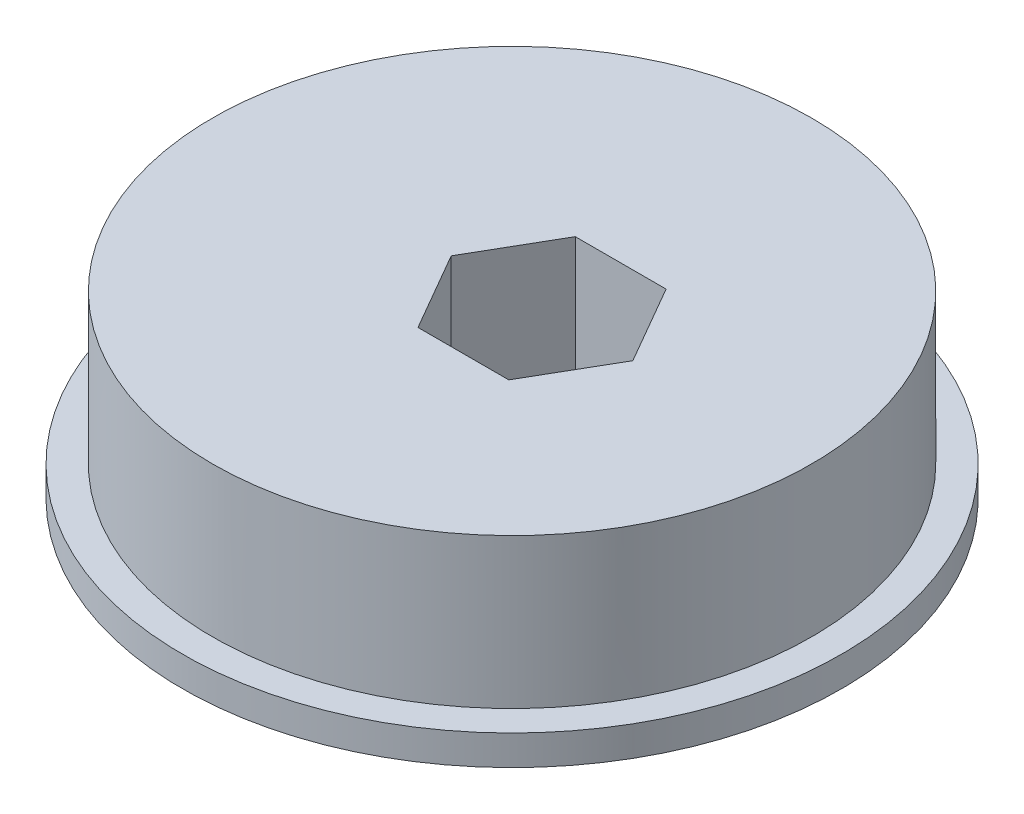
SolidWorks part; units mm, degrees
ref_plane "Front Plane" through (0, 0, 0) normal (0, 0, 1) x (1, 0, 0)
ref_plane "Top Plane" through (0, 0, 0) normal (0, 1, 0) x (1, 0, 0)
ref_plane "Right Plane" through (0, 0, 0) normal (1, 0, 0) x (0, 0, -1)
sketch "Sketch1" plane through (0, 0, 0) normal (0, 1, 0) x (1, 0, 0)
  line L0 (0, 0) -> (-1, 0) construction
  circle A1 centre (-1, 0) radius 10
  point P12 (0, 0)
  dimension "D3" = 20
  dimension "D2" = 1
extrude "Boss-Extrude1" add sketch "Sketch1" along normal blind 6
sketch "Sketch2" plane through (0, 0, 0) normal (0, -1, 0) x (1, 0, 0)
  line L0 (-12.8187, 0) -> (7.6603, 0) construction
  circle A0 centre (-1, 0) radius 11
  dimension "D2" = 22
  dimension "D1" = 1
extrude "Boss-Extrude2" add sketch "Sketch2" against normal blind 1
sketch "Sketch4" plane through (0, 6, 0) normal (0, 1, 0) x (1, 0, 0)
  line L0 (0, 8.8969) -> (0, -8.7328) construction
  line L2 (3.0311, 0) -> (1.5155, 2.625)
  line L3 (1.5155, 2.625) -> (-1.5155, 2.625)
  line L4 (-1.5155, 2.625) -> (-3.0311, 0)
  line L5 (-3.0311, 0) -> (-1.5155, -2.625)
  line L6 (-1.5155, -2.625) -> (1.5155, -2.625)
  line L7 (1.5155, -2.625) -> (3.0311, 0)
  circle A0 centre (0, 0) radius 5.5 construction
  circle A3 centre (0, 0) radius 2.625 construction
  dimension "D1" = 11
  dimension "D2" = 5.25
extrude "Cut-Extrude1" cut sketch "Sketch4" against normal through all
